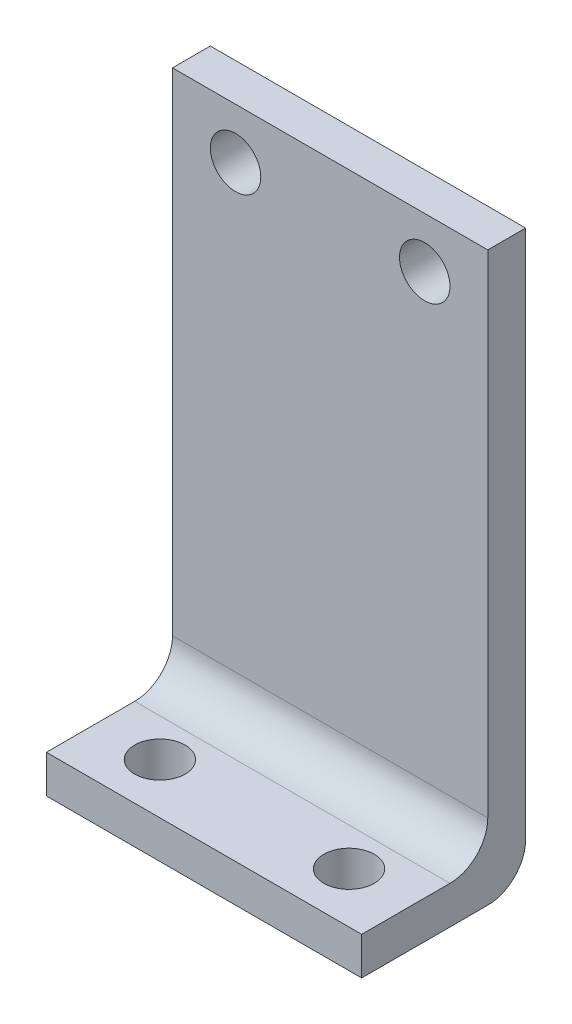
SolidWorks part; units mm, degrees
note: The reader was unsure of these and kept them because the rebuilt part matched: shared geometry of "Sketch1<3>".
ref_plane "Front Plane" through (0, 0, 0) normal (0, 0, 1) x (1, 0, 0)
ref_plane "Top Plane" through (0, 0, 0) normal (0, 1, 0) x (1, 0, 0)
ref_plane "Right Plane" through (0, 0, 0) normal (1, 0, 0) x (0, 0, -1)
sketch "Sketch1" plane through (0, 0, 0) normal (0, 0, 1) x (1, 0, 0)
  line L0 (-5.7412, 41) -> (27.1924, 41) construction
  line L1 (0, 0) -> (25, 0)
  line L2 (0, 0) -> (0, 45)
  line L3 (0, 45) -> (25, 45)
  line L4 (25, 0) -> (25, 45)
  line L5 (0, 0) -> (25, 0)
  line L6 (0, 0) -> (0, 3)
  line L7 (0, 3) -> (25, 3)
  line L8 (25, 0) -> (25, 3)
  circle A0 centre (5, 41) radius 2
  circle A1 centre (20, 41) radius 2
  point P5 (5, 41)
  point P10 (20, 41)
  dimension "D5" = 15
  dimension "D6" = 4
  dimension "D7" = 4
  dimension "D1" = 25
  dimension "D2" = 4
  dimension "D3" = 45
  dimension "D4" = 5
  dimension "D9" = 3
extrude "Boss-Extrude1" add sketch "Sketch1" against normal blind 3
extrude "Boss-Extrude2" add sketch "Sketch1<3>" along normal blind 13 from offset 3 contours L7 L2 L1 L4 offset against normal yes
sketch "Sketch1<3>" plane through (0, 0, 0) normal (0, 0, 1) x (1, 0, 0) same geometry as "Sketch1"
fillet "Fillet1" radius 3 2 edges at (12.5, 3, 0) (12.5, 0, -3)
sketch "Sketch2" plane through (0, 0, 0) normal (0, -1, 0) x (-1, 0, 0)
  line L0 (0, -10) -> (-25, -10) construction
  line L1 (0, 0) -> (0, -10) construction
  circle A0 centre (-5, -6) radius 2
  circle A1 centre (-20, -6) radius 2
  dimension "D3" = 4
  dimension "D4" = 4
  dimension "D1" = 4
  dimension "D2" = 5
  dimension "D5" = 15
  dimension "D6" = 4
extrude "Cut-Extrude1" cut sketch "Sketch2" against normal through all contours A0 | A1
